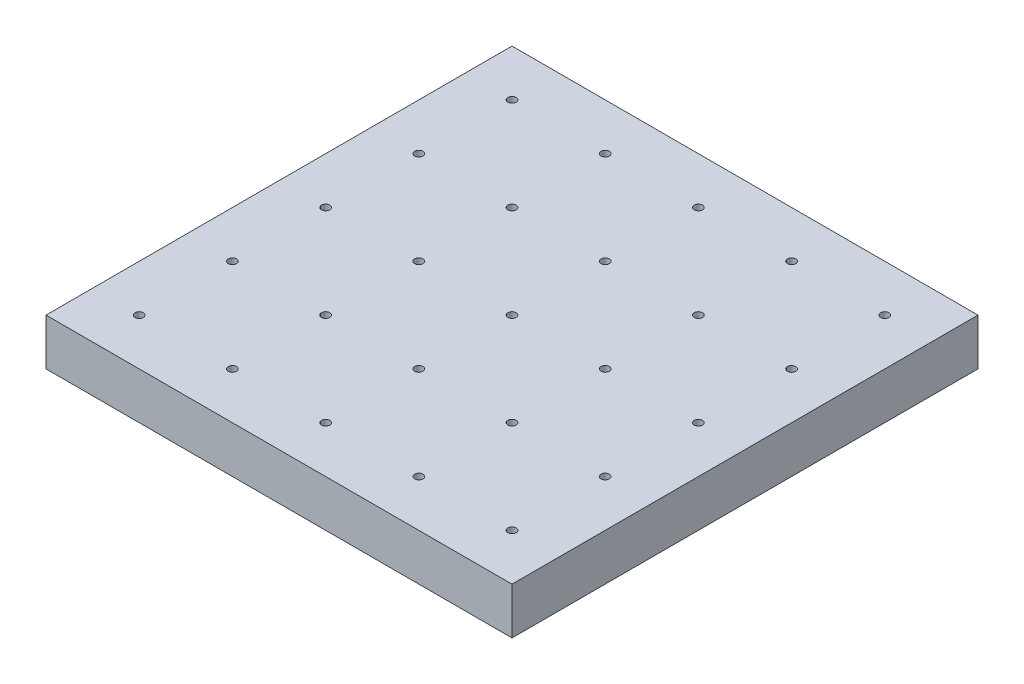
SolidWorks part; units mm, degrees
ref_plane "Front Plane" through (0, 0, 0) normal (0, 0, 1) x (1, 0, 0)
ref_plane "Top Plane" through (0, 0, 0) normal (0, 1, 0) x (1, 0, 0)
ref_plane "Right Plane" through (0, 0, 0) normal (1, 0, 0) x (0, 0, -1)
sketch "Sketch1" plane through (0, 0, 0) normal (0, 1, 0) x (1, 0, 0)
  line L1 (-63.5, 63.5) -> (63.5, 63.5)
  line L2 (-63.5, 63.5) -> (-63.5, -63.5)
  line L3 (-63.5, -63.5) -> (63.5, -63.5)
  line L4 (63.5, 63.5) -> (63.5, -63.5)
  line L5 (-63.5, 63.5) -> (63.5, -63.5) construction
  line L6 (-63.5, -63.5) -> (63.5, 63.5) construction
  point P0 (0, 0)
  dimension "D1" = 127
extrude "Boss-Extrude1" add sketch "Sketch1" along normal blind 12.7
hole_wizard "#4-40 Tapped Hole1" positions "3DSketch1" profile "Sketch2" tap size "#4-40" standard "ANSI Inch" end condition through all
sketch3d "3DSketch1"
  line L0 (-63.5, 12.7, 63.5) -> (63.5, 12.7, 63.5) construction
  line L1 (63.5, 12.7, 63.5) -> (63.5, 12.7, -63.5) construction
  point P0 (50.8, 12.7, 50.8)
  dimension "D2" = 12.7
  dimension "D1" = 12.7
cosmetic thread "Hole Thread1" parameters "D2"=2.8448
sketch "Sketch2" plane through (50.8, 12.7, 50.8) normal (1, 0, 0) x (0, 0, 1)
  line L0 (0, 0) -> (0, 12.7)
  line L1 (0, 12.7) -> (1.1303, 12.7)
  line L2 (1.1303, 12.7) -> (1.1303, 0)
  line L5 (1.1303, 0) -> (0, 0)
  line L11 (0, -6.35) -> (0, 107.95) construction
  dimension "Thru Tap Drill Dia." = 2.2606
  dimension "Thru Tap Drill Depth" = 12.7
pattern_linear "LPattern1" count 5 spacing 25.4 along (-1, 0, 0) count 5 spacing 25.4 along (0, 0, -1) of "#4-40 Tapped Hole1"
cosmetic thread "Hole Thread2" parameters "D2"=2.8448
cosmetic thread "Hole Thread3" parameters "D2"=2.8448
cosmetic thread "Hole Thread4" parameters "D2"=2.8448
cosmetic thread "Hole Thread5" parameters "D2"=2.8448
cosmetic thread "Hole Thread6" parameters "D2"=2.8448
cosmetic thread "Hole Thread7" parameters "D2"=2.8448
cosmetic thread "Hole Thread8" parameters "D2"=2.8448
cosmetic thread "Hole Thread9" parameters "D2"=2.8448
cosmetic thread "Hole Thread10" parameters "D2"=2.8448
cosmetic thread "Hole Thread11" parameters "D2"=2.8448
cosmetic thread "Hole Thread12" parameters "D2"=2.8448
cosmetic thread "Hole Thread13" parameters "D2"=2.8448
cosmetic thread "Hole Thread14" parameters "D2"=2.8448
cosmetic thread "Hole Thread15" parameters "D2"=2.8448
cosmetic thread "Hole Thread16" parameters "D2"=2.8448
cosmetic thread "Hole Thread17" parameters "D2"=2.8448
cosmetic thread "Hole Thread18" parameters "D2"=2.8448
cosmetic thread "Hole Thread19" parameters "D2"=2.8448
cosmetic thread "Hole Thread20" parameters "D2"=2.8448
cosmetic thread "Hole Thread21" parameters "D2"=2.8448
cosmetic thread "Hole Thread22" parameters "D2"=2.8448
cosmetic thread "Hole Thread23" parameters "D2"=2.8448
cosmetic thread "Hole Thread24" parameters "D2"=2.8448
cosmetic thread "Hole Thread25" parameters "D2"=2.8448
cosmetic thread "Hole Thread26" parameters "D2"=2.8448
cosmetic thread "Hole Thread27" parameters "D2"=2.8448
cosmetic thread "Hole Thread28" parameters "D2"=2.8448
cosmetic thread "Hole Thread29" parameters "D2"=2.8448
cosmetic thread "Hole Thread30" parameters "D2"=2.8448
cosmetic thread "Hole Thread31" parameters "D2"=2.8448
cosmetic thread "Hole Thread32" parameters "D2"=2.8448
cosmetic thread "Hole Thread33" parameters "D2"=2.8448
cosmetic thread "Hole Thread34" parameters "D2"=2.8448
cosmetic thread "Hole Thread35" parameters "D2"=2.8448
cosmetic thread "Hole Thread36" parameters "D2"=2.8448
equation "\"D2@3DSketch1\"=\"D1@3DSketch1\""
